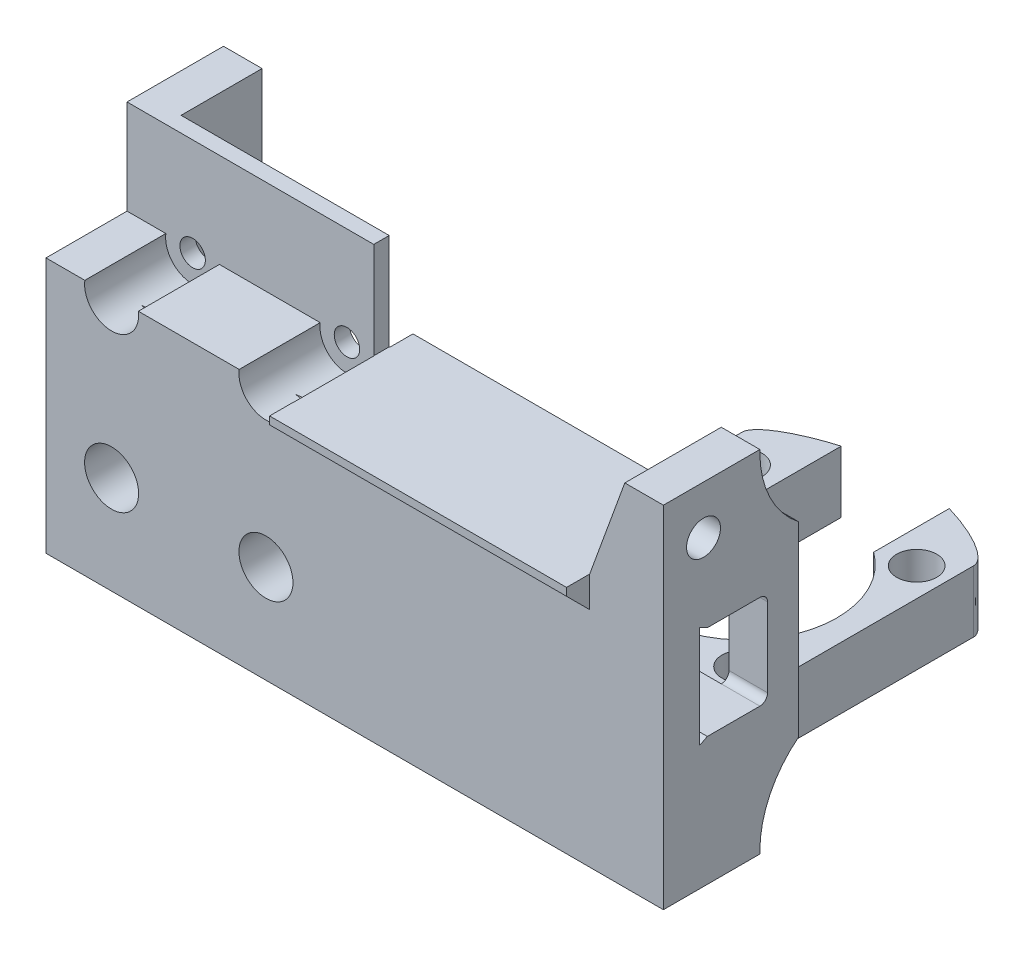
SolidWorks part; units mm, degrees
ref_plane "Front Plane" through (0, 0, 0) normal (0, 0, 1) x (1, 0, 0)
ref_plane "Top Plane" through (0, 0, 0) normal (0, 1, 0) x (1, 0, 0)
ref_plane "Right Plane" through (0, 0, 0) normal (1, 0, 0) x (0, 0, -1)
sketch "Sketch1" plane through (0, 0, 0) normal (0, 0, 1) x (1, 0, 0)
  line L1 (0, 0) -> (80, 0)
  line L2 (0, 0) -> (0, 45.4)
  line L3 (0, 45.4) -> (80, 45.4)
  line L4 (80, 0) -> (80, 45.4)
  line L5 (8.5, 32.7) -> (28.5, 32.7) construction
  line L6 (8.5, 32.7) -> (8.5, 12.7) construction
  line L7 (8.5, 12.7) -> (28.5, 12.7) construction
  line L8 (28.5, 32.7) -> (28.5, 12.7) construction
  circle A0 centre (8.5, 32.7) radius 1.65
  circle A1 centre (28.5, 32.7) radius 1.65
  circle A2 centre (28.5, 12.7) radius 1.65
  circle A3 centre (8.5, 12.7) radius 1.65
  dimension "D3" = 3.3
  dimension "D1" = 45.4
  dimension "D2" = 80
  dimension "D4" = 12.7
  dimension "D5" = 20
  dimension "D6" = 8.5
extrude "Boss-Extrude1" add sketch "Sketch1" along normal blind 12.5
sketch "Sketch2" plane through (0, 0, 0) normal (0, 0, -1) x (-1, 0, 0)
  line L0 (0, 0) -> (-80, 0) construction
  line L1 (0, 45.4) -> (-5, 45.4)
  line L2 (0, 45.4) -> (0, 0)
  line L3 (0, 0) -> (-5, 0)
  line L4 (-5, 45.4) -> (-5, 0)
  dimension "D1" = 5
extrude "Boss-Extrude2" add sketch "Sketch2" along normal blind 10.5
sketch "Sketch3" plane through (0, 0, 0) normal (0, 0, 1) x (1, 0, 0)
  line L0 (80, 0) -> (80, 45.4) construction
  line L1 (80, 28.8) -> (0, 28.8)
  line L2 (80, 28.8) -> (80, 16.6)
  line L3 (80, 16.6) -> (0, 16.6)
  line L4 (0, 28.8) -> (0, 16.6)
  line L5 (0, 0) -> (0, 45.4) construction
  line L6 (80, 22.7) -> (0, 22.7) construction
  point P10 (80, 22.7)
  dimension "D1" = 12.2
extrude "Cut-Extrude1" cut sketch "Sketch3" against normal through all and the other way blind 7.8
sketch "Sketch4" plane through (0, 0, 0) normal (0, 0, -1) x (-1, 0, 0)
  line L1 (-69.5, 0) -> (-39.5, 0)
  line L2 (-69.5, 0) -> (-69.5, 8)
  line L3 (-69.5, 8) -> (-39.5, 8)
  line L4 (-39.5, 0) -> (-39.5, 8)
  line L7 (-5, 0) -> (-80, 0) construction
  dimension "D1" = 8
  dimension "D2" = 30
  dimension "D3" = 39.5
extrude "Boss-Extrude3" add sketch "Sketch4" along normal blind 44.2
sketch "Sketch5" plane through (0, 8, 0) normal (0, 1, 0) x (1, 0, 0)
  line L0 (69.5, 44.2) -> (69.5, 0) construction
  line L1 (80, 0) -> (5, 0) construction
  circle A0 centre (54.4956, 23.5) radius 12
  dimension "D1" = 24
  dimension "D2" = 15.0044
  dimension "D3" = 23.5
extrude "Cut-Extrude2" cut sketch "Sketch5" against normal blind 45
sketch "Sketch6" plane through (0, 16.6, 0) normal (0, -1, 0) x (1, 0, 0)
  circle A3 centre (54.4956, -39.2013) radius 2.6
  circle A4 centre (65.8093, -34.515) radius 2.6
  circle A5 centre (43.1819, -34.515) radius 2.6
  circle A6 centre (43.1819, -11.8876) radius 2.6
  circle A7 centre (65.8093, -11.8876) radius 2.6
  dimension "D1" = 5.2
extrude "Cut-Extrude3" cut sketch "Sketch6" against normal through all both and the other way through all
fillet "Fillet1" radius 6 2 edges at (39.5, 4, -44.2) (69.5, 4, -44.2) second distance 15 conic rho 0.3 first distance on face at (39.5, 4, -22.1) first distance on face at (69.5, 4, -22.1)
sketch "Sketch8" plane through (0, 0, 12.5) normal (0, 0, 1) x (1, 0, 0)
  circle A0 centre (8.5, 32.7) radius 3.5
  circle A1 centre (28.5, 32.7) radius 3.5
  circle A2 centre (8.5, 12.7) radius 3.5
  circle A3 centre (28.5, 12.7) radius 3.5
  dimension "D1" = 7
extrude "Cut-Extrude5" cut sketch "Sketch8" against normal offset from surface (10.5 mm away) 2 up to face at (10.15, 12.7, 0)
sketch "Sketch12" plane through (0, 0, 12.5) normal (0, 0, 1) x (1, 0, 0)
  line L0 (80, 45.4) -> (0, 45.4) construction
  line L5 (0, 45.4) -> (45, 45.4)
  line L6 (0, 45.4) -> (0, 33.15)
  line L7 (0, 33.15) -> (45, 33.15)
  line L8 (45, 45.4) -> (45, 33.15)
  line L9 (0, 45.4) -> (0, 0) construction
  dimension "D1" = 12.25
  dimension "D2" = 45
extrude "Cut-Extrude8" cut sketch "Sketch12" against normal offset from surface (10.5 mm away) 2 up to face at (10.15, 32.7, 0)
sketch "Sketch13" plane through (0, 8, 0) normal (0, 1, 0) x (1, 0, 0)
  line L1 (61.4956, 50.8384) -> (47.4956, 50.8384)
  line L2 (61.4956, 50.8384) -> (61.4956, 27.5643)
  line L3 (61.4956, 27.5643) -> (47.4956, 27.5643)
  line L4 (47.4956, 50.8384) -> (47.4956, 27.5643)
  line L5 (61.4956, 50.8384) -> (47.4956, 27.5643) construction
  line L6 (61.4956, 27.5643) -> (47.4956, 50.8384) construction
  point P0 (54.4956, 39.2013)
  dimension "D1" = 14
extrude "Cut-Extrude10" cut sketch "Sketch13" against normal blind 10
sketch "Sketch14" plane through (0, 0, 0) normal (0, 0, -1) x (-1, 0, 0)
  line L1 (-80, 28.8) -> (0, 28.8)
  line L2 (-80, 28.8) -> (-80, 16.6)
  line L3 (-80, 16.6) -> (0, 16.6)
  line L4 (0, 28.8) -> (0, 16.6)
extrude "Boss-Extrude5" [suppressed] add sketch "Sketch14" against normal blind 0.5
sketch "Sketch15" plane through (0, 8, 0) normal (0, 1, 0) x (1, 0, 0)
  circle A0 centre (54.4956, 7.2013) radius 2.75
  dimension "D1" = 5.5
extrude "Boss-Extrude6" add sketch "Sketch15" along normal blind 2
sketch "Sketch16" plane through (0, 45.4, 0) normal (0, 1, 0) x (1, 0, 0)
  line L0 (39.5, 0) -> (69.5, 0) construction
  line L1 (75, 0) -> (31.9709, 0)
  line L2 (75, 0) -> (75, -12.5)
  line L3 (75, -12.5) -> (31.9709, -12.5)
  line L4 (31.9709, 0) -> (31.9709, -12.5)
  line L5 (80, -12.5) -> (45, -12.5) construction
  line L6 (80, -12.5) -> (80, 0) construction
  line L7 (31.9709, -12.5) -> (31.9709, -2) construction
  dimension "D2" = 5
extrude "Cut-Extrude11" cut sketch "Sketch16" against normal blind 12.5
chamfer "Chamfer2" distance 12.5 angle 20 1 edges at (75, 32.9, 6.25) first distance on face at (75, 39.15, 6.25)
sketch "Sketch17" plane through (80, 0, 0) normal (1, 0, 0) x (0, 0, -1)
  line L0 (-12.5, 45.4) -> (0, 45.4) construction
  line L1 (-12.5, 0) -> (-12.5, 45.4) construction
  circle A0 centre (-7.3, 39.15) radius 2.2
  point P4 (-6.7214, 39.15)
  dimension "D1" = 4.4
  dimension "D2" = 6.25
  dimension "D3" = 5.2
extrude "Cut-Extrude12" cut sketch "Sketch17" against normal blind 10
sketch "Sketch18" plane through (80, 0, 0) normal (1, 0, 0) x (0, 0, -1)
  line L0 (-7.8, 28.8) -> (-6.8, 28.8)
  line L1 (-7.8, 28.8) -> (0, 28.8) construction
  line L2 (-6.8, 28.8) -> (-7.8, 29.3)
  line L3 (-7.8, 29.3) -> (-7.8, 28.8)
  line L4 (-7.8, 16.6) -> (-7.8, 16.1)
  line L5 (-7.8, 16.1) -> (-6.8, 16.6)
  line L6 (-7.8, 16.6) -> (0, 16.6) construction
  line L7 (-6.8, 16.6) -> (-7.8, 16.6)
  dimension "D1" = 0.5
  dimension "D2" = 1
  dimension "D3" = 1
  dimension "D4" = 0.5
extrude "Cut-Extrude13" cut sketch "Sketch18" against normal through all
sketch "Sketch19" plane through (0, 0, 0) normal (0, 0, -1) x (-1, 0, 0)
  line L0 (-80, 0) -> (-80, 16.6) construction
  line L1 (-75, 34.8) -> (-80, 34.8)
  line L2 (-75, 34.8) -> (-75, 10.6)
  line L3 (-75, 10.6) -> (-80, 10.6)
  line L4 (-80, 34.8) -> (-80, 10.6)
  line L5 (-5, 16.6) -> (-80, 16.6) construction
  line L6 (-80, 28.8) -> (-5, 28.8) construction
  dimension "D1" = 6
  dimension "D2" = 6
extrude "Boss-Extrude7" add sketch "Sketch19" along normal blind 5
sketch "Sketch20" plane through (80, 0, 0) normal (1, 0, 0) x (0, 0, -1)
  line L0 (0, 28.8) -> (0, 16.6)
  line L1 (0, 28.8) -> (1, 28.8)
  line L2 (0, 16.6) -> (1, 16.6)
  line L3 (1, 28.8) -> (1, 16.6)
  dimension "D1" = 1
extrude "Cut-Extrude14" cut sketch "Sketch20" against normal through all
sketch "Sketch21" plane through (0, 16.6, 0) normal (0, 1, 0) x (1, 0, 0)
  line L0 (5, 0) -> (5, 10.5) construction
  line L1 (0, 10.5) -> (5, 10.5)
  line L2 (0, 10.5) -> (0, 1)
  line L3 (0, 1) -> (5, 1)
  line L4 (5, 10.5) -> (5, 1)
  dimension "D1" = 9.5
extrude "Boss-Extrude8" add sketch "Sketch21" along normal up to surface (12.2 mm away) up to face at (40, 28.8, -1.175)
fillet "Fillet2" radius 1 4 edges at (77.5, 16.6, -1) (77.5, 28.8, -1) (2.5, 16.6, -1) (2.5, 28.8, -1)
fillet "Fillet3" radius 13 2 edges at (77.5, 10.6, 0) (77.5, 34.8, 0)
chamfer "Chamfer1" distance 2 angle 45 1 edges at (54.4956, 10, -4.4513)
sketch "Sketch22" plane through (0, 0, 12.5) normal (0, 0, 1) x (1, 0, 0)
  line L1 (70.4504, 32.9) -> (31.9709, 32.9)
  line L2 (70.4504, 32.9) -> (70.4504, 31.9)
  line L3 (70.4504, 31.9) -> (31.9709, 31.9)
  line L4 (31.9709, 32.9) -> (31.9709, 31.9)
  line L5 (70.4504, 32.9) -> (31.9709, 31.9) construction
  line L6 (70.4504, 31.9) -> (31.9709, 32.9) construction
  line L7 (31.9709, 32.9) -> (31.9709, 45.4) construction
  point P4 (51.2107, 32.4)
  dimension "D1" = 1
extrude "Boss-Extrude9" add sketch "Sketch22" along normal blind 3
sketch "Sketch23" plane through (0, 0, 0) normal (0, 0, -1) x (-1, 0, 0)
  line L1 (-70.4504, 32.9) -> (-32.0504, 32.9)
  line L2 (-70.4504, 32.9) -> (-70.4504, 31.9)
  line L3 (-70.4504, 31.9) -> (-32.0504, 31.9)
  line L4 (-32.0504, 32.9) -> (-32.0504, 31.9)
  line L5 (-70.4504, 32.9) -> (-32.0504, 31.9) construction
  line L6 (-70.4504, 31.9) -> (-32.0504, 32.9) construction
  point P4 (-51.2504, 32.4)
  dimension "D1" = 1
  dimension "D2" = 38.4
extrude "Boss-Extrude10" add sketch "Sketch23" along normal blind 3
chamfer "Chamfer3" distance 3 angle 45 2 edges at (51.2107, 31.9, 12.5) (51.2504, 31.9, 0)
